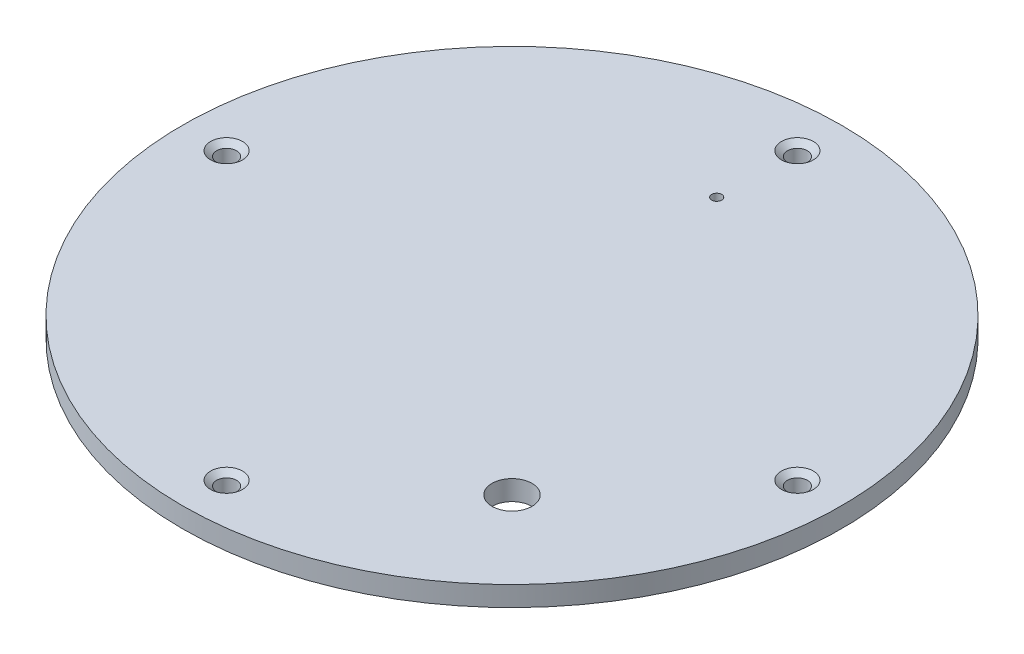
SolidWorks part; units mm, degrees
material "1060 Alloy"
ref_plane "Front Plane" through (0, 0, 0) normal (0, 0, 1) x (1, 0, 0)
ref_plane "Top Plane" through (0, 0, 0) normal (0, 1, 0) x (1, 0, 0)
ref_plane "Right Plane" through (0, 0, 0) normal (1, 0, 0) x (0, 0, -1)
sketch "Sketch1" plane through (0, 0, 0) normal (0, 1, 0) x (1, 0, 0)
  circle A0 centre (0, 0) radius 16.5
  dimension "D1" = 33
extrude "Boss-Extrude1" add sketch "Sketch1" along normal blind 1
hole_wizard "CSK for M2 Flat Head Machine Screw1" positions "Sketch2" profile "Sketch3" countersink size "M2" standard "ANSI Metric" end condition through all
sketch "Sketch2" plane through (0, 1, 0) normal (0, 1, 0) x (1, 0, 0)
  point P0 (0, 14.29)
  point P2 (14.29, 0)
  point P4 (0, -14.29)
  point P6 (-14.29, 0)
  dimension "D1" = 14.29
  dimension "D2" = 14.29
  dimension "D3" = 14.29
  dimension "D4" = 14.29
sketch "Sketch3" plane through (0, 1, -14.29) normal (1, 0, 0) x (0, 0, 1)
  line L0 (0, 0) -> (0, 1)
  line L1 (0, 1) -> (0.5, 1)
  line L2 (0.5, 1) -> (0.5, 0.2517)
  line L3 (0.5, 0.2517) -> (0.8, 0)
  line L5 (0.8, 0) -> (0, 0)
  line L6 (-0.5, 0.2517) -> (-0.8, 0) construction
  line L11 (0, -6.35) -> (0, 107.95) construction
  dimension "Thru Hole Dia." = 1
  dimension "Thru Hole Depth" = 1
  dimension "Near C'Sink Dia." = 1.6
  dimension "Near C'Sink Angle" = 100
sketch "Sketch4" plane through (0, 1, 0) normal (0, 1, 0) x (1, 0, 0)
  circle A0 centre (0, 10.25) radius 0.25
  dimension "D1" = 0.5
  dimension "D2" = 10.25
extrude "Cut-Extrude1" cut sketch "Sketch4" against normal through all both and the other way through all
sketch "Sketch5" plane through (0, 0, 0) normal (0, -1, 0) x (1, 0, 0)
  line L0 (0, 0) -> (12.768, 12.768) construction
  line L1 (0, 0) -> (24.3444, 0) construction
  circle A0 centre (7.7782, 7.7782) radius 1
  dimension "D2" = 2
  dimension "D1" = 11
  dimension "D3" = 45
extrude "Cut-Extrude2" cut sketch "Sketch5" against normal through all both and the other way through all
